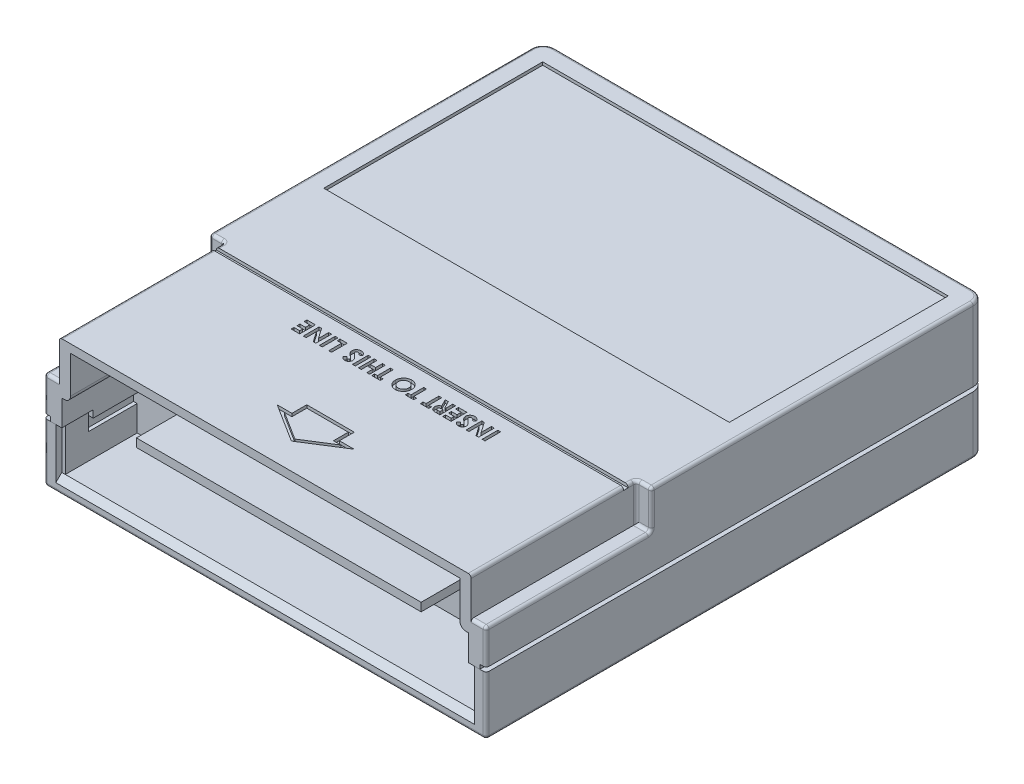
SolidWorks part; units mm, degrees
other "PCB"
other "Back"
other "Front"
ref_plane "Front Plane" through (0, 0, 0) normal (0, 0, 1) x (1, 0, 0)
ref_plane "Top Plane" through (0, 0, 0) normal (0, 1, 0) x (1, 0, 0)
ref_plane "Right Plane" through (0, 0, 0) normal (1, 0, 0) x (0, 0, -1)
sketch "Sketch1" plane through (0, 0, 0) normal (0, 1, 0) x (1, 0, 0)
  line L0 (0, 0) -> (0, 65.8) construction
  line L1 (-23.975, 0) -> (-23.975, 21.47)
  line L2 (-23.975, 21.47) -> (-26.93, 21.47)
  line L3 (-26.93, 21.47) -> (-26.93, 65.8)
  line L4 (-26.93, 65.8) -> (26.93, 65.8)
  line L5 (26.93, 65.8) -> (26.93, 21.47)
  line L6 (26.93, 21.47) -> (23.975, 21.47)
  line L7 (23.975, 21.47) -> (23.975, 0)
  line L8 (23.975, 0) -> (-23.975, 0)
  line L9 (-20.025, 17.13) -> (20.025, 17.13) construction
  circle A0 centre (-20.025, 19.03) radius 1.9
  circle A1 centre (0, 19.03) radius 2.65
  circle A2 centre (20.025, 19.03) radius 1.9
  point P16 (0, 0)
  dimension "D5" = 3.8
  dimension "D8" = 5.3
  dimension "D1" = 53.86
  dimension "D2" = 44.33
  dimension "D3" = 65.8
  dimension "D4" = 47.95
  dimension "D6" = 36.25
  dimension "D7" = 17.13
extrude "Boss-Extrude1" add sketch "Sketch1" along normal mid plane 1.6
sketch "Sketch2" plane through (0, 0.8, 0) normal (0, 1, 0) x (1, 0, 0)
  line L0 (0, 0) -> (0, 65.8) construction
  line L1 (-26.125, 39.52) -> (26.125, 39.52)
  line L2 (-26.125, 39.52) -> (-26.125, 25.82)
  line L3 (-26.125, 25.82) -> (26.125, 25.82)
  line L4 (26.125, 39.52) -> (26.125, 25.82)
  line L5 (26.93, 65.8) -> (-26.93, 65.8) construction
  line L6 (-23.975, 0) -> (23.975, 0) construction
  dimension "D1" = 52.25
  dimension "D2" = 13.7
  dimension "D3" = 25.82
extrude "Boss-Extrude2" add sketch "Sketch2" along normal blind 4.4
sketch "Sketch3" plane through (0, 0.8, 0) normal (0, 1, 0) x (1, 0, 0)
  line L0 (26.93, 21.47) -> (26.93, 65.8) construction
  line L1 (11.66, 63.46) -> (22.66, 63.46)
  line L2 (11.66, 63.46) -> (11.66, 42.86)
  line L3 (11.66, 42.86) -> (22.66, 42.86)
  line L4 (22.66, 63.46) -> (22.66, 42.86)
  line L5 (26.93, 65.8) -> (-26.93, 65.8) construction
  dimension "D1" = 20.6
  dimension "D2" = 11
  dimension "D3" = 4.27
  dimension "D4" = 2.34
extrude "Boss-Extrude3" add sketch "Sketch3" along normal blind 2.88
sketch "Sketch4" plane through (0, 0.8, 0) normal (0, 1, 0) x (1, 0, 0)
  line L0 (26.93, 65.8) -> (-26.93, 65.8) construction
  line L1 (0, 54.1) -> (0, 19.03) construction
  circle A0 centre (0, 54.1) radius 1.6
  dimension "D1" = 3.2
  dimension "D2" = 10.1
extrude "Boss-Extrude4" add sketch "Sketch4" along normal blind 6.75
sketch "Sketch5" plane through (0, 0.8, 0) normal (0, 1, 0) x (1, 0, 0)
  line L0 (23.975, 0) -> (23.975, 21.47) construction
  line L1 (-23.975, 0) -> (23.975, 0)
  line L2 (-23.975, 0) -> (-23.975, 8.52)
  line L3 (-23.975, 8.52) -> (23.975, 8.52)
  line L4 (23.975, 0) -> (23.975, 8.52)
  dimension "D1" = 8.52
extrude "Cut-Extrude1" cut sketch "Sketch5" against normal blind 0.1
mirror "Mirror1" about plane through (0, 0, 0) normal (0, 1, 0) of "Cut-Extrude1"
ref_plane "Plane1" through (0, -4.72, 0) normal (0, -1, 0) x (-1, 0, 0)
sketch "Sketch6" plane through (0, -4.72, 0) normal (0, -1, 0) x (-1, 0, 0)
  line L0 (0, 19.03) -> (0, 38.8) construction
  line L1 (-11.845, 38.8) -> (11.845, 38.8)
  line L2 (-11.845, 38.8) -> (-11.845, 80.73)
  line L3 (-11.845, 80.73) -> (11.845, 80.73)
  line L4 (11.845, 38.8) -> (11.845, 80.73)
  line L5 (23.975, 0) -> (-23.975, 0) construction
  dimension "D1" = 41.93
  dimension "D2" = 23.69
  dimension "D3" = 38.8
extrude "Boss-Extrude5" add sketch "Sketch6" along normal blind 1.09 separate body
sketch "Sketch7" plane through (0, -4.72, 0) normal (0, 1, 0) x (1, 0, 0)
  line L0 (0, 80.73) -> (0, 47.8) construction
  line L1 (-7.5, 47.8) -> (7.5, 47.8)
  line L2 (-7.5, 47.8) -> (-7.5, 43.8)
  line L3 (-7.5, 43.8) -> (7.5, 43.8)
  line L4 (7.5, 47.8) -> (7.5, 43.8)
  line L5 (-11.845, 80.73) -> (11.845, 80.73) construction
  line L6 (11.845, 38.8) -> (-11.845, 38.8) construction
  dimension "D1" = 15
  dimension "D2" = 4
  dimension "D3" = 5
extrude "Boss-Extrude6" add sketch "Sketch7" along normal up to next
sketch "Sketch8" plane through (0, -4.72, 0) normal (0, 1, 0) x (1, 0, 0)
  line L0 (-5, 80.73) -> (-3.795, 79.37)
  line L1 (-11.845, 80.73) -> (11.845, 80.73) construction
  line L2 (-3.795, 79.37) -> (3.795, 79.37)
  line L3 (3.795, 79.37) -> (5, 80.73)
  line L4 (5, 80.73) -> (-5, 80.73)
  line L5 (0, 79.37) -> (0, 65.8) construction
  line L6 (26.93, 65.8) -> (-26.93, 65.8) construction
  dimension "D1" = 7.59
  dimension "D2" = 1.36
  dimension "D3" = 10
extrude "Cut-Extrude2" cut sketch "Sketch8" against normal through all both and the other way through all
sketch "Sketch9" plane through (0, -4.72, 0) normal (0, 1, 0) x (1, 0, 0)
  line L0 (0, 79.37) -> (0, 77.88) construction
  line L1 (-7.5, 77.88) -> (7.5, 77.88)
  line L2 (-7.5, 77.88) -> (-7.5, 62.13)
  line L3 (-7.5, 62.13) -> (7.5, 62.13)
  line L4 (7.5, 77.88) -> (7.5, 62.13)
  line L5 (-3.795, 79.37) -> (3.795, 79.37) construction
  line L6 (-11.845, 80.73) -> (-5, 80.73) construction
  dimension "D1" = 15
  dimension "D2" = 2.85
  dimension "D3" = 15.75
extrude "Boss-Extrude7" add sketch "Sketch9" along normal blind 1.95
sketch "Sketch10" plane through (0, 0.8, 0) normal (0, 1, 0) x (1, 0, 0)
  line L0 (0, 0) -> (0, 87.284) construction
  circle A0 centre (-20.025, 19.03) radius 1.73
  circle A1 centre (0, 19.03) radius 2.47
  circle A2 centre (20.025, 19.03) radius 1.73
  circle A3 centre (0, 19.03) radius 1.515
  circle A4 centre (-27, 73.03) radius 3.28
  circle A5 centre (27, 73.03) radius 3.28
  circle A6 centre (-27, 73.03) radius 1.515
  circle A7 centre (27, 73.03) radius 1.515
  dimension "D1" = 3.46
  dimension "D2" = 4.94
  dimension "D3" = 3.03
  dimension "D4" = 6.56
  dimension "D5" = 54
  dimension "D6" = 54
extrude "Boss-Extrude8" add sketch "Sketch10" against normal up to surface (1.6 mm away) separate body up to face at (0, -0.8, -16.38)
sketch "Sketch11" plane through (0, -0.8, 0) normal (0, -1, 0) x (1, 0, 0)
  circle A0 centre (20.025, -19.03) radius 2.5
  circle A1 centre (-20.025, -19.03) radius 2.5
  circle A2 centre (0, -19.03) radius 1.515
  circle A3 centre (0, -19.03) radius 3.28
  circle A4 centre (0, -19.03) radius 1.515 construction
  circle A5 centre (27, -73.03) radius 3.28 construction
  circle A6 centre (-27, -73.03) radius 3.28 construction
  circle A7 centre (27, -73.03) radius 3.28
  circle A8 centre (-27, -73.03) radius 3.28
  circle A9 centre (-27, -73.03) radius 1.515 construction
  circle A10 centre (27, -73.03) radius 1.515 construction
  circle A11 centre (-27, -73.03) radius 1.515
  circle A12 centre (27, -73.03) radius 1.515
  dimension "D1" = 5
  dimension "D2" = 6.56
extrude "Boss-Extrude9" add sketch "Sketch11" along normal blind 8.535 separate body
sketch "Sketch12" plane through (0, -9.335, 0) normal (0, -1, 0) x (1, 0, 0)
  circle A0 centre (0, -19.03) radius 1.515
  circle A1 centre (0, -19.03) radius 4.625
  circle A2 centre (0, -19.03) radius 1.515 construction
  circle A3 centre (-27, -73.03) radius 4.625
  circle A4 centre (27, -73.03) radius 4.625
  circle A5 centre (-27, -73.03) radius 1.515
  circle A6 centre (27, -73.03) radius 1.515
  dimension "D1" = 9.25
extrude "Boss-Extrude10" add sketch "Sketch12" against normal blind 2.3 separate body
sketch "Sketch13" plane through (0, -9.335, 0) normal (0, -1, 0) x (1, 0, 0)
  line L0 (-37.215, 2.285) -> (37.215, 2.285)
  line L1 (37.215, 2.285) -> (37.215, -81.73)
  line L2 (37.215, -81.73) -> (-37.215, -81.73)
  line L3 (-37.215, -81.73) -> (-37.215, 2.285)
  line L4 (0, 0) -> (0, 2.285) construction
  line L5 (-11.845, -80.73) -> (-5, -80.73) construction
  circle A0 centre (0, -19.03) radius 1.515 construction
  circle A1 centre (0, -19.03) radius 1.515 construction
  circle A2 centre (0, -19.03) radius 1.515
  circle A3 centre (27, -73.03) radius 1.515 construction
  circle A4 centre (-27, -73.03) radius 1.515 construction
  circle A5 centre (27, -73.03) radius 1.515
  circle A6 centre (-27, -73.03) radius 1.515
  dimension "D3" = 19.8
  dimension "D1" = 74.43
  dimension "D2" = 1
extrude "Boss-Extrude11" add sketch "Sketch13" along normal blind 2.35 separate body
fillet "Fillet1" radius 2 2 edges at (37.215, -10.51, -81.73) (-37.215, -10.51, -81.73)
sketch "Sketch14" plane through (0, -9.335, 0) normal (0, 1, 0) x (1, 0, 0)
  line L0 (-35.265, -2.285) -> (-35.265, 77.43)
  line L1 (-33.265, 79.43) -> (33.265, 79.43)
  line L2 (35.265, 77.43) -> (35.265, -2.285)
  line L3 (35.265, -2.285) -> (37.215, -2.285)
  line L4 (37.215, -2.285) -> (37.215, 79.73)
  line L5 (35.215, 81.73) -> (-35.215, 81.73)
  line L6 (-37.215, 79.73) -> (-37.215, -2.285)
  line L7 (-37.215, -2.285) -> (37.215, -2.285)
  line L8 (37.215, -2.285) -> (37.215, 79.73)
  line L9 (35.215, 81.73) -> (-35.215, 81.73)
  line L10 (-37.215, 79.73) -> (-37.215, -2.285)
  line L11 (-37.215, -2.285) -> (-35.265, -2.285)
  arc A0 (33.265, 79.43) -> (35.265, 77.43) centre (33.265, 77.43) cw
  arc A1 (-35.265, 77.43) -> (-33.265, 79.43) centre (-33.265, 77.43) cw
  arc A2 (37.215, 79.73) -> (35.215, 81.73) centre (35.215, 79.73) ccw
  arc A3 (-35.215, 81.73) -> (-37.215, 79.73) centre (-35.215, 79.73) ccw
  arc A4 (37.215, 79.73) -> (35.215, 81.73) centre (35.215, 79.73) ccw
  arc A5 (-35.215, 81.73) -> (-37.215, 79.73) centre (-35.215, 79.73) ccw
  dimension "D5" = 2
  dimension "D2" = 1.95
  dimension "D3" = 2.3
  dimension "D4" = 1.95
  dimension "D1" = 0
extrude "Boss-Extrude12" add sketch "Sketch14" along normal blind 7.49 separate body
combine bodies "Combine1" operation type add bodies to combine 111 119 118 117 116 115 114 113 112 119 118 117 116 115 114 113 112 152 151 148 153 150 149
sketch "Sketch21" plane through (0, 0, -79.43) normal (0, 0, 1) x (1, 0, 0)
  line L0 (11.845, -5.81) -> (-11.845, -5.81) construction
  line L1 (-12.345, -2.47) -> (12.345, -2.47)
  line L2 (-12.345, -2.47) -> (-12.345, -6.06)
  line L3 (-12.345, -6.06) -> (12.345, -6.06)
  line L4 (12.345, -2.47) -> (12.345, -6.06)
  line L5 (-11.845, -5.81) -> (-11.845, -4.72) construction
  line L6 (11.845, -5.81) -> (11.845, -4.72) construction
  line L7 (-7.5, -2.77) -> (7.5, -2.77) construction
  dimension "D1" = 0.25
  dimension "D2" = 0.5
  dimension "D3" = 0.5
  dimension "D4" = 0.3
extrude "Cut-Extrude4" cut sketch "Sketch21" against normal blind 1.4 and the other way blind 10
chamfer "Chamfer1" distance 1 angle 45 1 edges at (0, -9.335, 2.285)
ref_plane "Plane2" through (0, 0, -10.815) normal (0, 0, 1) x (1, 0, 0)
sketch "Sketch15" plane through (0, -9.335, 0) normal (0, 1, 0) x (1, 0, 0)
  line L0 (35.265, 77.43) -> (35.265, -2.285) construction
  line L1 (-33.265, 79.43) -> (33.265, 79.43) construction
  line L2 (-35.265, -1.285) -> (-35.265, 77.43) construction
  line L3 (35.265, 77.43) -> (35.265, -1.285)
  line L4 (-33.265, 79.43) -> (33.265, 79.43)
  line L5 (-35.265, -1.285) -> (-35.265, 77.43)
  line L6 (-34.665, -1.285) -> (-34.665, 77.43)
  line L7 (-33.265, 78.83) -> (33.265, 78.83)
  line L8 (34.665, 77.43) -> (34.665, -1.285)
  line L11 (-35.265, -1.285) -> (-34.665, -1.285)
  line L12 (34.665, -1.285) -> (35.265, -1.285)
  line L13 (35.265, -2.285) -> (-35.265, -2.285) construction
  line L14 (35.265, 77.43) -> (35.265, -2.285) construction
  line L15 (34.665, 77.43) -> (34.665, -2.285) construction
  line L17 (-35.265, -1.285) -> (-35.265, 77.43) construction
  line L18 (-34.665, -1.285) -> (-34.665, 77.43) construction
  arc A0 (35.265, 77.43) -> (33.265, 79.43) centre (33.265, 77.43) ccw construction
  arc A1 (-33.265, 79.43) -> (-35.265, 77.43) centre (-33.265, 77.43) ccw construction
  arc A2 (35.265, 77.43) -> (33.265, 79.43) centre (33.265, 77.43) ccw
  arc A3 (-33.265, 79.43) -> (-35.265, 77.43) centre (-33.265, 77.43) ccw
  arc A4 (-33.265, 78.83) -> (-34.665, 77.43) centre (-33.265, 77.43) ccw
  arc A5 (34.665, 77.43) -> (33.265, 78.83) centre (33.265, 77.43) ccw
  dimension "D2" = 1
  dimension "D1" = 0.6
extrude "Boss-Extrude13" add sketch "Sketch15" along normal blind 4.3
sketch "Sketch17" plane through (0, -5.035, 0) normal (0, 1, 0) x (1, 0, 0)
  line L0 (-35.265, -2.285) -> (-35.265, 77.43) construction
  line L1 (-34.665, -1.285) -> (-35.265, -1.285)
  line L2 (-34.665, -1.285) -> (-34.665, 2.615)
  line L3 (-34.665, 2.615) -> (-35.265, 2.615)
  line L4 (-35.265, -1.285) -> (-35.265, 2.615)
  dimension "D1" = 3.9
extrude "Boss-Extrude14" add sketch "Sketch17" along normal up to surface (3.19 mm away) up to face at (0, -1.845, -52.4297)
mirror "Mirror2" about plane through (0, 0, 0) normal (1, 0, 0) of "Boss-Extrude14"
sketch "Sketch18" plane through (0, 0, -10.815) normal (0, 0, 1) x (1, 0, 0)
  line L0 (-34.665, -9.335) -> (-34.665, -5.035)
  line L1 (-34.665, -5.035) -> (-35.265, -5.035)
  line L2 (-35.265, -5.035) -> (-35.265, -3.095)
  line L3 (-35.265, -1.845) -> (-35.265, -10.335) construction
  line L4 (-35.265, -3.095) -> (-33.965, -3.095)
  line L5 (-33.965, -3.095) -> (-33.965, 1.21)
  line L6 (-33.965, 1.21) -> (-24.215, 1.21)
  line L7 (-24.215, 1.21) -> (-24.215, -1.09)
  line L8 (-24.215, -1.09) -> (24.215, -1.09)
  line L9 (24.215, -1.09) -> (24.215, 1.21)
  line L10 (24.215, 1.21) -> (33.965, 1.21)
  line L11 (33.965, 1.21) -> (33.965, -3.095)
  line L12 (33.965, -3.095) -> (35.265, -3.095)
  line L13 (35.265, -3.095) -> (35.265, -5.035)
  line L14 (35.265, -5.035) -> (34.665, -5.035)
  line L15 (34.665, -5.035) -> (34.665, -9.335)
  line L16 (34.665, -9.335) -> (-34.665, -9.335)
  line L17 (-37.215, -1.845) -> (-35.265, -1.845) construction
  line L18 (0, -9.335) -> (0, -1.09) construction
  line L19 (-37.215, -1.845) -> (-37.215, -11.685) construction
  dimension "D1" = 1.25
  dimension "D2" = 9.75
  dimension "D3" = 3.25
  dimension "D4" = 10.545
  dimension "D5" = 8.245
extrude "Boss-Extrude15" add sketch "Sketch18" against normal blind 1.7
sketch "Sketch19" plane through (0, -9.335, 0) normal (0, 1, 0) x (1, 0, 0)
  line L0 (0, 0) -> (0, 7.9552) construction
  line L1 (-34.665, 12.515) -> (34.665, 12.515) construction
  circle A0 centre (-20, 57.515) radius 3
  circle A1 centre (20, 57.515) radius 3
  dimension "D2" = 6
  dimension "D3" = 45
  dimension "D1" = 40
extrude "Boss-Extrude16" add sketch "Sketch19" along normal up to next
sketch "Sketch20" plane through (0, -11.685, 0) normal (0, -1, 0) x (1, 0, 0)
  circle A0 centre (0, -19.03) radius 2.95
  circle A1 centre (-27, -73.03) radius 2.95
  circle A2 centre (27, -73.03) radius 2.95
  dimension "D1" = 5.9
extrude "Cut-Extrude3" cut sketch "Sketch20" against normal blind 2.45
sketch "Sketch23" plane through (0, 0, -81.73) normal (0, 0, -1) x (-1, 0, 0)
  line L0 (-7.5, -2.77) -> (-7.5, -4.72) construction
  line L1 (-8, -4.97) -> (8, -4.97)
  line L2 (-8, -4.97) -> (-8, -2.52)
  line L3 (-8, -2.52) -> (8, -2.52)
  line L4 (8, -4.97) -> (8, -2.52)
  line L5 (7.5, -2.77) -> (7.5, -4.72) construction
  line L6 (-7.5, -2.77) -> (7.5, -2.77) construction
  line L7 (3.795, -4.72) -> (-3.795, -4.72) construction
  dimension "D1" = 0.5
  dimension "D2" = 0.5
  dimension "D3" = 0.25
  dimension "D4" = 0.25
extrude "Cut-Extrude5" cut sketch "Sketch23" along normal through all and the other way blind 30.88
fillet "Fillet2" radius 0.5 8 edges at (-37.215, -11.685, -38.7225) (-36.6292, -11.685, -81.1442) (0, -11.685, -81.73) (36.6292, -11.685, -81.1442) (37.215, -11.685, -38.7225) (0, -11.685, 2.285) (37.215, -6.765, 2.285) (-37.215, -6.765, 2.285)
sketch "Sketch39" plane through (0, 0, -78.83) normal (0, 0, 1) x (1, 0, 0)
  line L1 (-12.345, -5.035) -> (12.345, -5.035)
  line L2 (-12.345, -5.035) -> (-12.345, -6.06)
  line L3 (-12.345, -6.06) -> (12.345, -6.06)
  line L4 (12.345, -5.035) -> (12.345, -6.06)
extrude "Cut-Extrude11" cut sketch "Sketch39" against normal up to surface (0.6 mm away) up to face at (0, -5.5475, -79.43)
sketch "Sketch24" plane through (0, -1.845, 0) normal (0, 1, 0) x (1, 0, 0)
  line L0 (35.265, 77.43) -> (35.265, 2.615) construction
  line L1 (-33.265, 79.43) -> (33.265, 79.43) construction
  line L2 (-35.265, 2.615) -> (-35.265, 77.43) construction
  line L3 (35.265, 77.43) -> (35.265, 2.615)
  line L4 (-33.265, 79.43) -> (33.265, 79.43)
  line L5 (-35.265, 2.615) -> (-35.265, 77.43)
  line L6 (-36.145, 2.615) -> (-36.145, 77.43)
  line L7 (-33.265, 80.31) -> (33.265, 80.31)
  line L8 (36.145, 77.43) -> (36.145, 2.615)
  line L9 (-35.265, 2.615) -> (-35.265, -2.285)
  line L10 (-35.265, -2.285) -> (-36.145, -2.285)
  line L11 (-36.145, -2.285) -> (-36.145, 2.615)
  line L12 (35.265, 2.615) -> (35.265, -2.285)
  line L13 (35.265, -2.285) -> (36.145, -2.285)
  line L14 (36.145, -2.285) -> (36.145, 2.615)
  arc A0 (35.265, 77.43) -> (33.265, 79.43) centre (33.265, 77.43) ccw construction
  arc A1 (-33.265, 79.43) -> (-35.265, 77.43) centre (-33.265, 77.43) ccw construction
  arc A2 (35.265, 77.43) -> (33.265, 79.43) centre (33.265, 77.43) ccw
  arc A3 (-33.265, 79.43) -> (-35.265, 77.43) centre (-33.265, 77.43) ccw
  arc A4 (-33.265, 80.31) -> (-36.145, 77.43) centre (-33.265, 77.43) ccw
  arc A5 (36.145, 77.43) -> (33.265, 80.31) centre (33.265, 77.43) ccw
  dimension "D1" = 0.88
extrude "Boss-Extrude17" add sketch "Sketch24" along normal blind 0.72 separate body
sketch "Sketch25" plane through (0, -1.125, 0) normal (0, 1, 0) x (1, 0, 0)
  line L1 (-37.215, 79.73) -> (-37.215, -1.785) construction
  line L2 (35.215, 81.73) -> (-35.215, 81.73) construction
  line L3 (37.215, -1.785) -> (37.215, 79.73) construction
  line L5 (35.265, 77.43) -> (35.265, -2.285) construction
  line L6 (-33.265, 79.43) -> (33.265, 79.43) construction
  line L7 (-35.265, -2.285) -> (-35.265, 77.43) construction
  line L9 (-37.215, 79.73) -> (-37.215, -1.785)
  line L10 (35.215, 81.73) -> (-35.215, 81.73)
  line L11 (37.215, -1.785) -> (37.215, 79.73)
  line L13 (35.265, 77.43) -> (35.265, -2.285)
  line L14 (-33.265, 79.43) -> (33.265, 79.43)
  line L15 (-35.265, -2.285) -> (-35.265, 77.43)
  line L16 (-36.715, -2.285) -> (-35.265, -2.285) construction
  line L17 (-36.715, -2.285) -> (-35.265, -2.285)
  line L18 (35.265, -2.285) -> (36.715, -2.285) construction
  line L19 (35.265, -2.285) -> (36.715, -2.285)
  arc A0 (-35.215, 81.73) -> (-37.215, 79.73) centre (-35.215, 79.73) ccw construction
  arc A1 (37.215, 79.73) -> (35.215, 81.73) centre (35.215, 79.73) ccw construction
  arc A2 (35.265, 77.43) -> (33.265, 79.43) centre (33.265, 77.43) ccw construction
  arc A3 (-33.265, 79.43) -> (-35.265, 77.43) centre (-33.265, 77.43) ccw construction
  arc A4 (-35.215, 81.73) -> (-37.215, 79.73) centre (-35.215, 79.73) ccw
  arc A5 (37.215, 79.73) -> (35.215, 81.73) centre (35.215, 79.73) ccw
  arc A6 (35.265, 77.43) -> (33.265, 79.43) centre (33.265, 77.43) ccw
  arc A7 (-33.265, 79.43) -> (-35.265, 77.43) centre (-33.265, 77.43) ccw
  arc A8 (-37.215, -1.785) -> (-36.715, -2.285) centre (-36.715, -1.785) ccw construction
  arc A9 (-37.215, -1.785) -> (-36.715, -2.285) centre (-36.715, -1.785) ccw
  arc A10 (36.715, -2.285) -> (37.215, -1.785) centre (36.715, -1.785) ccw construction
  arc A11 (36.715, -2.285) -> (37.215, -1.785) centre (36.715, -1.785) ccw
extrude "Boss-Extrude18" add sketch "Sketch25" along normal blind 12.29 separate body
sketch "Sketch26" plane through (0, 11.165, 0) normal (0, 1, 0) x (1, 0, 0)
  line L0 (35.265, 77.43) -> (35.265, -2.285) construction
  line L1 (-33.265, 79.43) -> (33.265, 79.43) construction
  line L2 (-35.265, -2.285) -> (-35.265, 77.43) construction
  line L3 (35.265, 77.43) -> (35.265, -2.285)
  line L4 (-33.265, 79.43) -> (33.265, 79.43)
  line L5 (-35.265, -2.285) -> (-35.265, 77.43)
  line L6 (-35.265, -2.285) -> (35.265, -2.285)
  arc A0 (35.265, 77.43) -> (33.265, 79.43) centre (33.265, 77.43) ccw construction
  arc A1 (-33.265, 79.43) -> (-35.265, 77.43) centre (-33.265, 77.43) ccw construction
  arc A2 (35.265, 77.43) -> (33.265, 79.43) centre (33.265, 77.43) ccw
  arc A3 (-33.265, 79.43) -> (-35.265, 77.43) centre (-33.265, 77.43) ccw
extrude "Boss-Extrude19" add sketch "Sketch26" against normal blind 2.39 separate body
sketch "Sketch28" plane through (0, 0, 2.285) normal (0, 0, 1) x (1, 0, 0)
  line L1 (-35.265, 8.775) -> (-32.795, 8.775)
  line L2 (-35.265, 8.775) -> (-35.265, 2.515)
  line L3 (-35.265, 2.515) -> (-32.795, 2.515)
  line L4 (-32.795, 8.775) -> (-32.795, 2.515)
  line L5 (35.265, 8.775) -> (32.795, 8.775)
  line L6 (35.265, 8.775) -> (35.265, 2.515)
  line L7 (35.265, 2.515) -> (32.795, 2.515)
  line L8 (32.795, 8.775) -> (32.795, 2.515)
  dimension "D1" = 2.47
  dimension "D2" = 6.26
extrude "Boss-Extrude20" add sketch "Sketch28" against normal blind 30.88 separate body
combine bodies "Combine2" operation type add bodies to combine 134 131 133 130 129
sketch "Sketch29" plane through (0, 11.165, 0) normal (0, 1, 0) x (1, 0, 0)
  line L0 (-37.215, 79.73) -> (-37.215, -1.785) construction
  line L1 (-37.215, 25.525) -> (-34.685, 25.525)
  line L2 (-37.215, 25.525) -> (-37.215, -2.285)
  line L3 (-37.215, -2.285) -> (-34.685, -2.285)
  line L4 (-34.685, 25.525) -> (-34.685, -2.285)
  line L5 (-36.715, -2.285) -> (36.715, -2.285) construction
  line L6 (37.215, -1.785) -> (37.215, 79.73) construction
  line L7 (37.215, 25.525) -> (34.685, 25.525)
  line L8 (37.215, 25.525) -> (37.215, -2.285)
  line L9 (37.215, -2.285) -> (34.685, -2.285)
  line L10 (34.685, 25.525) -> (34.685, -2.285)
  line L11 (0, 0) -> (0, 27.6033) construction
  dimension "D1" = 2.53
  dimension "D2" = 27.81
extrude "Cut-Extrude6" cut sketch "Sketch29" against normal blind 6.42
sketch "Sketch30" plane through (0, 0, -10.815) normal (0, 0, 1) x (1, 0, 0)
  line L0 (-32.795, 8.775) -> (32.795, 8.775)
  line L1 (32.795, 8.775) -> (32.795, 2.515)
  line L2 (32.795, 2.515) -> (35.265, 2.515)
  line L3 (35.265, 2.515) -> (35.265, 1.21)
  line L4 (35.265, 2.515) -> (35.265, -1.845) construction
  line L5 (35.265, 1.21) -> (-35.265, 1.21)
  line L6 (-35.265, 8.775) -> (-35.265, -1.845) construction
  line L7 (-35.265, 1.21) -> (-35.265, 2.515)
  line L8 (-35.265, 2.515) -> (-32.795, 2.515)
  line L9 (-32.795, 2.515) -> (-32.795, 8.775)
  line L10 (-24.215, 1.21) -> (-33.965, 1.21) construction
extrude "Boss-Extrude21" add sketch "Sketch30" against normal up to surface (1.7 mm away) up to face at (0, -3.0331, -12.515)
ref_plane "Plane3" through (0, -3.075, 0) normal (0, -1, 0) x (-1, 0, 0)
sketch "Sketch31" plane through (0, -3.075, 0) normal (0, -1, 0) x (-1, 0, 0)
  line L0 (35.265, -2.285) -> (35.265, 77.43) construction
  line L1 (-33.265, 79.43) -> (33.265, 79.43) construction
  line L2 (-35.265, 77.43) -> (-35.265, -2.285) construction
  line L3 (35.265, -2.285) -> (35.265, 77.43)
  line L4 (-33.265, 79.43) -> (33.265, 79.43)
  line L5 (-35.265, 77.43) -> (-35.265, -2.285)
  line L6 (34.265, -2.285) -> (34.265, 77.43)
  line L7 (-33.265, 78.43) -> (33.265, 78.43)
  line L8 (-34.265, 77.43) -> (-34.265, -2.285)
  line L9 (-35.265, -2.285) -> (-34.265, -2.285)
  line L10 (34.265, -2.285) -> (35.265, -2.285)
  arc A0 (35.265, 77.43) -> (33.265, 79.43) centre (33.265, 77.43) ccw construction
  arc A1 (-33.265, 79.43) -> (-35.265, 77.43) centre (-33.265, 77.43) ccw construction
  arc A2 (35.265, 77.43) -> (33.265, 79.43) centre (33.265, 77.43) ccw
  arc A3 (-33.265, 79.43) -> (-35.265, 77.43) centre (-33.265, 77.43) ccw
  arc A4 (34.265, 77.43) -> (33.265, 78.43) centre (33.265, 77.43) ccw
  arc A5 (-33.265, 78.43) -> (-34.265, 77.43) centre (-33.265, 77.43) ccw
  dimension "D1" = 1
extrude "Boss-Extrude22" add sketch "Sketch31" against normal up to next
sketch "Sketch32" plane through (0, -3.075, 0) normal (0, -1, 0) x (1, 0, 0)
  line L0 (-35.265, 2.285) -> (-35.265, -77.43) construction
  line L1 (-34.265, -10.815) -> (-35.265, -10.815)
  line L2 (-34.265, -10.815) -> (-34.265, -16.815)
  line L3 (-34.265, -16.815) -> (-35.265, -16.815)
  line L4 (-35.265, -10.815) -> (-35.265, -16.815)
  line L5 (0, 0) -> (0, -20.9928) construction
  line L6 (35.265, -10.815) -> (35.265, -16.815)
  line L7 (34.265, -16.815) -> (35.265, -16.815)
  line L8 (34.265, -10.815) -> (34.265, -16.815)
  line L9 (34.265, -10.815) -> (35.265, -10.815)
  dimension "D1" = 6
extrude "Cut-Extrude7" cut sketch "Sketch32" against normal up to surface (4.285 mm away) up to face at (0, 1.21, -11.665)
sketch "Sketch33" plane through (0, 1.21, 0) normal (0, -1, 0) x (1, 0, 0)
  line L1 (-34.265, -12.515) -> (-35.265, -12.515)
  line L2 (-34.265, -12.515) -> (-34.265, -16.815)
  line L3 (-34.265, -16.815) -> (-35.265, -16.815)
  line L4 (-35.265, -12.515) -> (-35.265, -16.815)
  line L5 (34.265, -12.515) -> (35.265, -12.515)
  line L6 (34.265, -12.515) -> (34.265, -16.815)
  line L7 (34.265, -16.815) -> (35.265, -16.815)
  line L8 (35.265, -12.515) -> (35.265, -16.815)
extrude "Cut-Extrude8" cut sketch "Sketch33" against normal up to surface (1.305 mm away) up to face at (-33.53, 2.515, -20.555)
sketch "Sketch34" plane through (0, -3.075, 0) normal (0, -1, 0) x (1, 0, 0)
  line L0 (-34.265, -10.815) -> (-34.265, 2.285) construction
  line L1 (-35.265, 2.285) -> (-34.265, 2.285)
  line L2 (-35.265, 2.285) -> (-35.265, -3.015)
  line L3 (-35.265, -3.015) -> (-34.265, -3.015)
  line L4 (-34.265, 2.285) -> (-34.265, -3.015)
  line L5 (34.265, 2.285) -> (34.265, -10.815) construction
  line L6 (35.265, 2.285) -> (34.265, 2.285)
  line L7 (35.265, 2.285) -> (35.265, -3.015)
  line L8 (35.265, -3.015) -> (34.265, -3.015)
  line L9 (34.265, 2.285) -> (34.265, -3.015)
  dimension "D1" = 5.3
extrude "Cut-Extrude9" cut sketch "Sketch34" against normal up to surface (1.23 mm away) up to face at (0, -1.845, -42.3338)
fillet "Fillet3" radius 1 6 edges at (32.795, 5.645, -28.595) (32.795, 2.515, -20.555) (-32.795, 5.645, -28.595) (-32.795, 2.515, -20.555) (-32.795, 2.515, -4.265) (32.795, 2.515, -4.265)
chamfer "Chamfer2" distance 1 angle 45 1 edges at (0, 8.775, 2.285)
sketch "Sketch35" plane through (0, 8.775, 0) normal (0, -1, 0) x (1, 0, 0)
  line L0 (0, 0) -> (0, -3.837) construction
  line L1 (33.265, -78.43) -> (-33.265, -78.43) construction
  circle A0 centre (-26, -65.43) radius 2.5
  circle A1 centre (26, -65.43) radius 2.5
  dimension "D1" = 5
  dimension "D2" = 13
  dimension "D3" = 52
extrude "Boss-Extrude23" add sketch "Sketch35" along normal up to surface (7.975 mm away) up to face at (0, 0.8, -55.7)
sketch "Sketch36" plane through (0, 8.775, 0) normal (0, -1, 0) x (1, 0, 0)
  circle A0 centre (0, -19.03) radius 1.515
  circle A1 centre (0, -19.03) radius 3.28
  circle A2 centre (-27, -73.03) radius 1.515
  circle A3 centre (-27, -73.03) radius 3.28
  circle A4 centre (27, -73.03) radius 1.515
  circle A5 centre (27, -73.03) radius 3.28
  dimension "D1" = 6.56
  dimension "D2" = 3.03
extrude "Boss-Extrude24" add sketch "Sketch36" along normal up to surface (7.975 mm away) up to face at (0, 0.8, -17.515)
sketch "Sketch38" plane through (0, 11.165, 0) normal (0, 1, 0) x (1, 0, 0)
  line L0 (-34.685, -2.285) -> (-34.685, 25.525) construction
  line L1 (-34.685, 24.165) -> (34.685, 24.165)
  line L2 (-34.685, 24.165) -> (-34.685, 23.395)
  line L3 (-34.685, 23.395) -> (34.685, 23.395)
  line L4 (34.685, 24.165) -> (34.685, 23.395)
  line L5 (34.685, 25.525) -> (34.685, -2.285) construction
  line L6 (-3.5, 5.715) -> (-3.5, 8.215)
  line L7 (-3.5, 8.215) -> (3.5, 8.215)
  line L8 (3.5, 8.215) -> (3.5, 5.715)
  line L9 (3.5, 5.715) -> (4.75, 5.715)
  line L10 (4.75, 5.715) -> (0, 2.715)
  line L11 (0, 2.715) -> (-4.75, 5.715)
  line L12 (-4.75, 5.715) -> (-3.5, 5.715)
  line L13 (-34.685, -2.285) -> (34.685, -2.285) construction
  line L14 (0, 0) -> (0, 8.215) construction
  line L15 (-4, 6.215) -> (-4, 8.715)
  line L16 (-4, 8.715) -> (4, 8.715)
  line L17 (4, 8.715) -> (4, 6.215)
  line L18 (4, 6.215) -> (6.478, 6.215)
  line L19 (6.478, 6.215) -> (0, 2.1236)
  line L20 (0, 2.1236) -> (-6.478, 6.215)
  line L21 (-6.478, 6.215) -> (-4, 6.215)
  line L22 (35.215, 81.73) -> (-35.215, 81.73) construction
  line L23 (34.685, 21.095) -> (-34.685, 21.095) construction
  line L24 (-34.15, 78.6) -> (34.15, 78.6)
  line L25 (-34.15, 78.6) -> (-34.15, 41.73)
  line L26 (-34.15, 41.73) -> (34.15, 41.73)
  line L27 (34.15, 78.6) -> (34.15, 41.73)
  line L28 (34.685, 25.525) -> (34.685, -2.285) construction
  text T0 "INSERT TO THIS LINE" font "Century Gothic" height in points 10
  dimension "D1" = 0.77
  dimension "D2" = 25.68
  dimension "D3" = 7
  dimension "D4" = 9.5
  dimension "D5" = 2.5
  dimension "D6" = 5.5
  dimension "D7" = 5
  dimension "D9" = 36.87
  dimension "D10" = 68.3
  dimension "D11" = 3.13
  dimension "D12" = 2.3
  dimension "D8" = 0.5
extrude "Cut-Extrude10" cut sketch "Sketch38" against normal blind 0.5
fillet "Fillet4" radius 0.5 23 edges at (-35.7, 4.745, 2.285) (35.7, 4.745, 2.285) (-37.0686, 4.745, 2.1386) (37.0686, 4.745, 2.1386) (-34.685, 11.165, -24.845) (-37.215, 4.745, -11.87) (34.685, 11.165, -24.845) (37.215, 4.745, -11.87) (-37.215, 11.165, -52.6275) (-36.6292, 11.165, -81.1442) (0, 11.165, -81.73) (36.6292, 11.165, -81.1442) (-34.685, 7.955, -25.525) (-35.95, 11.165, -25.525) (-37.215, 7.955, -25.525) (-35.95, 4.745, -25.525) (35.95, 11.165, -25.525) (34.685, 7.955, -25.525) (35.95, 4.745, -25.525) (37.215, 7.955, -25.525) (37.215, 11.165, -52.6275) (-34.685, 11.165, -10.555) (34.685, 11.165, -10.555)
sketch "Sketch40" plane through (0, 0, -79.43) normal (0, 0, -1) x (-1, 0, 0)
  line L0 (33.265, -3.075) -> (-33.265, -3.075) construction
  line L1 (-8.25, -3.075) -> (8.25, -3.075)
  line L2 (-8.25, -3.075) -> (-8.25, -2.225)
  line L3 (-8.25, -2.225) -> (8.25, -2.225)
  line L4 (8.25, -3.075) -> (8.25, -2.225)
  line L5 (0, 0) -> (0, -2.225) construction
  dimension "D1" = 0.85
  dimension "D2" = 16.5
extrude "Cut-Extrude12" cut sketch "Sketch40" against normal blind 10
